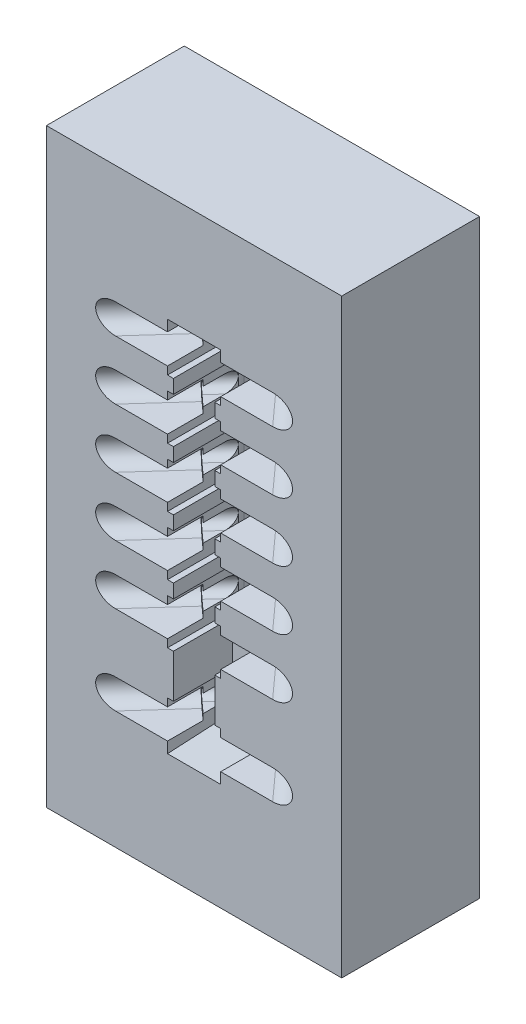
SolidWorks part; units mm, degrees
ref_plane "Front Plane" through (0, 0, 0) normal (0, 0, 1) x (1, 0, 0)
ref_plane "Top Plane" through (0, 0, 0) normal (0, 1, 0) x (1, 0, 0)
ref_plane "Right Plane" through (0, 0, 0) normal (1, 0, 0) x (0, 0, -1)
sketch "Sketch1" plane through (0, 0, 0) normal (0, 0, 1) x (1, 0, 0)
  line L0 (-7.5, 0) -> (0, 0) construction
  line L1 (-7.5, 15) -> (7.5, 15)
  line L2 (-7.5, 15) -> (-7.5, -15)
  line L3 (-7.5, -15) -> (7.5, -15)
  line L4 (7.5, 15) -> (7.5, -15)
  line L5 (0, 0) -> (0, 15) construction
  dimension "D1" = 15
  dimension "D2" = 30
sketch "Sketch2" plane through (0, 0, 0) normal (1, 0, 0) x (0, 0, -1)
  line L1 (0, 15) -> (7, 15)
  line L2 (0, 15) -> (0, -15)
  line L3 (0, -15) -> (7, -15)
  line L4 (7, 15) -> (7, -15)
  dimension "D1" = 7
extrude "Boss-Extrude1" add sketch "Sketch1" against normal up to vertex (7 mm away) up to point (0, 15, -7)
ref_plane "Plane1" through (1.35, 0, 0) normal (1, 0, 0) x (0, 0, -1)
sketch "Sketch7" plane through (1.35, 0, 0) normal (1, 0, 0) x (0, 0, -1)
  line L0 (3, 4.1005) -> (0, 4.1005) construction
  line L1 (0, 4.1005) -> (0, 6.3995) construction
  line L2 (3, 6.3995) -> (0, 6.3995) construction
  line L3 (3, 6.3995) -> (6.5, 6.2161) construction
  line L4 (6.5, 6.2161) -> (6.5, 4.2839) construction
  line L5 (6.5, 4.2839) -> (3, 4.1005) construction
  line L6 (3, 1.1005) -> (0, 1.1005) construction
  line L7 (0, 1.1005) -> (0, 3.3995) construction
  line L8 (3, 3.3995) -> (0, 3.3995) construction
  line L9 (6.5, 3.2161) -> (3, 3.3995) construction
  line L10 (6.5, 1.2839) -> (6.5, 3.2161) construction
  line L11 (3, 1.1005) -> (6.5, 1.2839) construction
  line L12 (3, -1.8995) -> (0, -1.8995) construction
  line L13 (0, -1.8995) -> (0, 0.3995) construction
  line L14 (3, 0.3995) -> (0, 0.3995) construction
  line L15 (3, 0.3995) -> (6.5, 0.2161) construction
  line L16 (6.5, 0.2161) -> (6.5, -1.7161) construction
  line L17 (6.5, -1.7161) -> (3, -1.8995) construction
  line L19 (3, -4.8995) -> (0, -4.8995) construction
  line L20 (0, -4.8995) -> (0, -2.6005) construction
  line L21 (3, -2.6005) -> (0, -2.6005) construction
  line L22 (6.5, -2.7839) -> (3, -2.6005) construction
  line L23 (6.5, -4.7161) -> (6.5, -2.7839) construction
  line L24 (3, -4.8995) -> (6.5, -4.7161) construction
  line L25 (3, -7.1005) -> (0, -7.1005) construction
  line L26 (0, -9.5567) -> (0, -7.1005) construction
  line L27 (6.5, -9.2161) -> (0, -9.5567) construction
  line L28 (6.5, -7.2839) -> (6.5, -9.2161) construction
  line L29 (3, -7.1005) -> (6.5, -7.2839) construction
  line L30 (3, 7.1005) -> (0, 7.1005) construction
  line L31 (0, 7.1005) -> (0, 9.5567) construction
  line L32 (6.5, 9.2161) -> (0, 9.5567) construction
  line L33 (6.5, 7.2839) -> (6.5, 9.2161) construction
  line L34 (3, 7.1005) -> (6.5, 7.2839) construction
  line L35 (3, 4.1005) -> (0, 4.1005)
  line L36 (0, 4.1005) -> (0, 6.3995)
  line L37 (3, 6.3995) -> (0, 6.3995)
  line L38 (3, 6.3995) -> (6.5, 6.2161)
  line L39 (6.5, 6.2161) -> (6.5, 4.2839)
  line L40 (6.5, 4.2839) -> (3, 4.1005)
  line L41 (3, 1.1005) -> (0, 1.1005)
  line L42 (0, 1.1005) -> (0, 3.3995)
  line L43 (3, 3.3995) -> (0, 3.3995)
  line L44 (6.5, 3.2161) -> (3, 3.3995)
  line L45 (6.5, 1.2839) -> (6.5, 3.2161)
  line L46 (3, 1.1005) -> (6.5, 1.2839)
  line L47 (3, -1.8995) -> (0, -1.8995)
  line L48 (0, -1.8995) -> (0, 0.3995)
  line L49 (3, 0.3995) -> (0, 0.3995)
  line L50 (3, 0.3995) -> (6.5, 0.2161)
  line L51 (6.5, 0.2161) -> (6.5, -1.7161)
  line L52 (6.5, -1.7161) -> (3, -1.8995)
  line L54 (3, -4.8995) -> (0, -4.8995)
  line L55 (0, -4.8995) -> (0, -2.6005)
  line L56 (3, -2.6005) -> (0, -2.6005)
  line L57 (6.5, -2.7839) -> (3, -2.6005)
  line L58 (6.5, -4.7161) -> (6.5, -2.7839)
  line L59 (3, -4.8995) -> (6.5, -4.7161)
  line L60 (3, -7.1005) -> (0, -7.1005)
  line L61 (0, -9.5567) -> (0, -7.1005)
  line L62 (6.5, -9.2161) -> (0, -9.5567)
  line L63 (6.5, -7.2839) -> (6.5, -9.2161)
  line L64 (3, -7.1005) -> (6.5, -7.2839)
  line L65 (3, 7.1005) -> (0, 7.1005)
  line L66 (0, 7.1005) -> (0, 9.5567)
  line L67 (6.5, 9.2161) -> (0, 9.5567)
  line L68 (6.5, 7.2839) -> (6.5, 9.2161)
  line L69 (3, 7.1005) -> (6.5, 7.2839)
sketch "Sketch8" plane through (1.35, 0, 0) normal (1, 0, 0) x (0, 0, -1)
  line L0 (6.5, -4.7161) -> (6.5, -2.7839) construction
  line L1 (6.5, -2.7839) -> (3, -2.6005) construction
  line L2 (3, -2.6005) -> (3, -1.8995) construction
  line L3 (6.5, -1.7161) -> (3, -1.8995) construction
  line L4 (6.5, 0.2161) -> (6.5, -1.7161) construction
  line L5 (3, 0.3995) -> (6.5, 0.2161) construction
  line L6 (3, 0.3995) -> (3, 1.1005) construction
  line L7 (3, 1.1005) -> (6.5, 1.2839) construction
  line L8 (6.5, 1.2839) -> (6.5, 3.2161) construction
  line L9 (6.5, 3.2161) -> (3, 3.3995) construction
  line L10 (3, 3.3995) -> (3, 4.1005) construction
  line L11 (6.5, 4.2839) -> (3, 4.1005) construction
  line L12 (6.5, 6.2161) -> (6.5, 4.2839) construction
  line L13 (3, 6.3995) -> (6.5, 6.2161) construction
  line L14 (3, 6.3995) -> (3, 7.1005) construction
  line L15 (3, 7.1005) -> (6.5, 7.2839) construction
  line L16 (6.5, 7.2839) -> (6.5, 9.2161) construction
  line L17 (6.5, 9.2161) -> (0, 9.5567) construction
  line L18 (0, 9.5567) -> (0, -9.5567) construction
  line L19 (6.5, -9.2161) -> (0, -9.5567) construction
  line L20 (6.5, -7.2839) -> (6.5, -9.2161) construction
  line L21 (3, -7.1005) -> (6.5, -7.2839) construction
  line L22 (3, -7.1005) -> (3, -4.8995) construction
  line L23 (3, -4.8995) -> (6.5, -4.7161) construction
  line L24 (6.5, -4.7161) -> (6.5, -2.7839)
  line L25 (6.5, -2.7839) -> (3, -2.6005)
  line L26 (3, -2.6005) -> (3, -1.8995)
  line L27 (6.5, -1.7161) -> (3, -1.8995)
  line L28 (6.5, 0.2161) -> (6.5, -1.7161)
  line L29 (3, 0.3995) -> (6.5, 0.2161)
  line L30 (3, 0.3995) -> (3, 1.1005)
  line L31 (3, 1.1005) -> (6.5, 1.2839)
  line L32 (6.5, 1.2839) -> (6.5, 3.2161)
  line L33 (6.5, 3.2161) -> (3, 3.3995)
  line L34 (3, 3.3995) -> (3, 4.1005)
  line L35 (6.5, 4.2839) -> (3, 4.1005)
  line L36 (6.5, 6.2161) -> (6.5, 4.2839)
  line L37 (3, 6.3995) -> (6.5, 6.2161)
  line L38 (3, 6.3995) -> (3, 7.1005)
  line L39 (3, 7.1005) -> (6.5, 7.2839)
  line L40 (6.5, 7.2839) -> (6.5, 9.2161)
  line L41 (6.5, 9.2161) -> (0, 9.5567)
  line L42 (0, 9.5567) -> (0, -9.5567)
  line L43 (6.5, -9.2161) -> (0, -9.5567)
  line L44 (6.5, -7.2839) -> (6.5, -9.2161)
  line L45 (3, -7.1005) -> (6.5, -7.2839)
  line L46 (3, -7.1005) -> (3, -4.8995)
  line L47 (3, -4.8995) -> (6.5, -4.7161)
sketch "Sketch9" plane through (0, 0, 0) normal (0, 0, 1) x (1, 0, 0)
  line L0 (-1.35, 9.5567) -> (-1.35, -9.5567) construction
  line L1 (1.35, -9.5567) -> (-1.35, -9.5567) construction
  line L2 (1.35, 9.5567) -> (1.35, -9.5567) construction
  line L3 (1.35, 9.5567) -> (-1.35, 9.5567) construction
  line L4 (-1.35, 9.5567) -> (-1.35, -9.5567) construction
  line L5 (1.35, -9.5567) -> (-1.35, -9.5567) construction
  line L6 (1.35, 9.5567) -> (1.35, -9.5567) construction
  line L7 (1.35, 9.5567) -> (-1.35, 9.5567) construction
  line L8 (0, -9.5567) -> (0, 9.5567) construction
  line L9 (-1.35, 0) -> (1.35, 0) construction
  line L10 (0.75, -9.1562) -> (-0.75, -9.1562) construction
  line L11 (-0.75, 9.1562) -> (-0.75, -9.1562) construction
  line L12 (0.75, 9.1562) -> (-0.75, 9.1562) construction
  line L13 (0.75, -9.1562) -> (-0.75, -9.1562)
  line L14 (-0.75, 9.1562) -> (-0.75, -9.1562)
  line L15 (0.75, 9.1562) -> (-0.75, 9.1562)
  line L16 (0.75, -9.1562) -> (0.75, 9.1562)
  line L17 (1.05, -9.5567) -> (1.05, 9.5567) construction
  line L18 (-1.05, -9.5567) -> (-1.05, 9.5567) construction
  line L19 (1.05, -9.5567) -> (1.05, 9.5567) construction
  line L20 (-1.05, -9.5567) -> (-1.05, 9.5567) construction
ref_plane "Plane2" through (0, -9.5567, 0) normal (0, 1, 0) x (1, 0, 0)
sketch "Sketch10" plane through (0, -9.5567, 0) normal (0, 1, 0) x (1, 0, 0)
  line L0 (1.35, 3.5995) -> (1.35, 6.5)
  line L1 (-1.35, 3.5995) -> (-1.35, 6.5)
  arc A0 (-1.2465, 3.7776) -> (-1.35, 6.5) centre (-4.95, 5) ccw construction
  arc A1 (-1.35, 3.5995) -> (-1.2465, 3.7776) centre (-1.7213, 3.9344) ccw construction
  arc A2 (1.2465, 3.7776) -> (1.35, 3.5995) centre (1.7213, 3.9344) ccw construction
  arc A3 (1.35, 6.5) -> (1.2465, 3.7776) centre (4.95, 5) ccw construction
  arc A4 (-1.2465, 3.7776) -> (-1.35, 6.5) centre (-4.95, 5) ccw
  arc A5 (-1.35, 3.5995) -> (-1.2465, 3.7776) centre (-1.7213, 3.9344) ccw
  arc A6 (1.2465, 3.7776) -> (1.35, 3.5995) centre (1.7213, 3.9344) ccw
  arc A7 (1.35, 6.5) -> (1.2465, 3.7776) centre (4.95, 5) ccw
ref_plane "Plane3" through (2.213, 9.1562, -4.3777) normal (0.6697, 0, 0.7426) x (0, -1, 0)
sketch "Sketch11" plane through (2.213, 9.1562, -4.3777) normal (0.6697, 0, 0.7426) x (0, -1, 0)
  line L0 (0.4562, -2.362) -> (0.4562, -1.612) construction
  line L1 (1.3562, -1.612) -> (1.3562, -2.362) construction
  line L2 (1.3562, -2.362) -> (0.4562, -2.362) construction
  line L3 (3.4562, -1.612) -> (3.4562, -2.362) construction
  line L4 (3.4562, -2.362) -> (4.3562, -2.362) construction
  line L5 (4.3562, -2.362) -> (4.3562, -1.612) construction
  line L6 (7.3562, -1.612) -> (7.3562, -2.362) construction
  line L7 (7.3562, -2.362) -> (6.4562, -2.362) construction
  line L8 (6.4562, -2.362) -> (6.4562, -1.612) construction
  line L9 (9.4562, -1.612) -> (9.4562, -2.362) construction
  line L10 (9.4562, -2.362) -> (10.3562, -2.362) construction
  line L11 (10.3562, -2.362) -> (10.3562, -1.612) construction
  line L12 (13.3562, -1.612) -> (13.3562, -2.362) construction
  line L13 (13.3562, -2.362) -> (12.4562, -2.362) construction
  line L14 (12.4562, -2.362) -> (12.4562, -1.612) construction
  line L15 (16.9562, -1.612) -> (16.9562, -2.362) construction
  line L16 (16.9562, -2.362) -> (17.8562, -2.362) construction
  line L17 (17.8562, -2.362) -> (17.8562, -1.612) construction
  line L18 (0.4562, -2.362) -> (0.4562, -1.612)
  line L19 (1.3562, -1.612) -> (1.3562, -2.362)
  line L20 (1.3562, -2.362) -> (0.4562, -2.362)
  line L21 (3.4562, -1.612) -> (3.4562, -2.362)
  line L22 (3.4562, -2.362) -> (4.3562, -2.362)
  line L23 (4.3562, -2.362) -> (4.3562, -1.612)
  line L24 (7.3562, -1.612) -> (7.3562, -2.362)
  line L25 (7.3562, -2.362) -> (6.4562, -2.362)
  line L26 (6.4562, -2.362) -> (6.4562, -1.612)
  line L27 (9.4562, -1.612) -> (9.4562, -2.362)
  line L28 (9.4562, -2.362) -> (10.3562, -2.362)
  line L29 (10.3562, -2.362) -> (10.3562, -1.612)
  line L30 (13.3562, -1.612) -> (13.3562, -2.362)
  line L31 (13.3562, -2.362) -> (12.4562, -2.362)
  line L32 (12.4562, -2.362) -> (12.4562, -1.612)
  line L33 (16.9562, -1.612) -> (16.9562, -2.362)
  line L34 (16.9562, -2.362) -> (17.8562, -2.362)
  line L35 (17.8562, -2.362) -> (17.8562, -1.612)
  line L36 (0.9062, -1.612) -> (0.9062, -1.162) construction
  line L37 (3.9062, -1.162) -> (3.9062, -1.612) construction
  line L38 (6.9062, -1.612) -> (6.9062, -1.162) construction
  line L39 (9.9062, -1.612) -> (9.9062, -1.162) construction
  line L40 (12.9062, -1.612) -> (12.9062, -1.162) construction
  line L41 (17.4062, -1.612) -> (17.4062, -1.162) construction
  line L42 (17.8562, -1.612) -> (16.9562, -1.612) construction
  line L43 (13.3562, -1.612) -> (12.4562, -1.612) construction
  line L44 (10.3562, -1.612) -> (9.4562, -1.612) construction
  line L46 (7.3562, -1.612) -> (6.4562, -1.612) construction
  line L47 (4.3562, -1.612) -> (3.4562, -1.612) construction
  line L48 (1.3562, -1.612) -> (0.4562, -1.612) construction
  arc A0 (1.3562, -1.612) -> (0.4562, -1.612) centre (0.9062, -1.612) ccw construction
  arc A1 (4.3562, -1.612) -> (3.4562, -1.612) centre (3.9062, -1.612) ccw construction
  arc A2 (7.3562, -1.612) -> (6.4562, -1.612) centre (6.9062, -1.612) ccw construction
  arc A3 (10.3562, -1.612) -> (9.4562, -1.612) centre (9.9062, -1.612) ccw construction
  arc A4 (13.3562, -1.612) -> (12.4562, -1.612) centre (12.9062, -1.612) ccw construction
  arc A5 (17.8562, -1.612) -> (16.9562, -1.612) centre (17.4062, -1.612) ccw construction
  arc A6 (1.3562, -1.612) -> (0.4562, -1.612) centre (0.9062, -1.612) ccw
  arc A7 (4.3562, -1.612) -> (3.4562, -1.612) centre (3.9062, -1.612) ccw
  arc A8 (7.3562, -1.612) -> (6.4562, -1.612) centre (6.9062, -1.612) ccw
  arc A9 (10.3562, -1.612) -> (9.4562, -1.612) centre (9.9062, -1.612) ccw
  arc A10 (13.3562, -1.612) -> (12.4562, -1.612) centre (12.9062, -1.612) ccw
  arc A11 (17.8562, -1.612) -> (16.9562, -1.612) centre (17.4062, -1.612) ccw
ref_plane "Plane4" through (3.1041, 9.1562, -3.3895) normal (0.6697, 0, 0.7426) x (0, -1, 0)
sketch "Sketch12" plane through (3.1041, 9.1562, -3.3895) normal (0.6697, 0, 0.7426) x (0, -1, 0)
  line L0 (0.1562, -1.612) -> (0.1562, -5.0612) construction
  line L1 (0.1562, -5.0612) -> (1.6562, -5.0612) construction
  line L2 (1.6562, -1.612) -> (1.6562, -5.0612) construction
  line L3 (3.1562, -1.612) -> (3.1562, -5.0612) construction
  line L4 (4.6562, -5.0612) -> (3.1562, -5.0612) construction
  line L5 (4.6562, -1.612) -> (4.6562, -5.0612) construction
  line L6 (6.1562, -1.612) -> (6.1562, -5.0612) construction
  line L7 (6.1562, -5.0612) -> (7.6562, -5.0612) construction
  line L8 (7.6562, -1.612) -> (7.6562, -5.0612) construction
  line L9 (9.1562, -1.612) -> (9.1562, -5.0612) construction
  line L10 (10.6562, -5.0612) -> (9.1562, -5.0612) construction
  line L11 (10.6562, -1.612) -> (10.6562, -5.0612) construction
  line L12 (12.1562, -1.612) -> (12.1562, -5.0612) construction
  line L13 (12.1562, -5.0612) -> (13.6562, -5.0612) construction
  line L14 (13.6562, -1.612) -> (13.6562, -5.0612) construction
  line L15 (16.6562, -1.612) -> (16.6562, -5.0612) construction
  line L16 (18.1562, -5.0612) -> (16.6562, -5.0612) construction
  line L17 (18.1562, -1.612) -> (18.1562, -5.0612) construction
  line L18 (0.1562, -1.612) -> (0.1562, -5.0612)
  line L19 (0.1562, -5.0612) -> (1.6562, -5.0612)
  line L20 (1.6562, -1.612) -> (1.6562, -5.0612)
  line L21 (3.1562, -1.612) -> (3.1562, -5.0612)
  line L22 (4.6562, -5.0612) -> (3.1562, -5.0612)
  line L23 (4.6562, -1.612) -> (4.6562, -5.0612)
  line L24 (6.1562, -1.612) -> (6.1562, -5.0612)
  line L25 (6.1562, -5.0612) -> (7.6562, -5.0612)
  line L26 (7.6562, -1.612) -> (7.6562, -5.0612)
  line L27 (9.1562, -1.612) -> (9.1562, -5.0612)
  line L28 (10.6562, -5.0612) -> (9.1562, -5.0612)
  line L29 (10.6562, -1.612) -> (10.6562, -5.0612)
  line L30 (12.1562, -1.612) -> (12.1562, -5.0612)
  line L31 (12.1562, -5.0612) -> (13.6562, -5.0612)
  line L32 (13.6562, -1.612) -> (13.6562, -5.0612)
  line L33 (16.6562, -1.612) -> (16.6562, -5.0612)
  line L34 (18.1562, -5.0612) -> (16.6562, -5.0612)
  line L35 (18.1562, -1.612) -> (18.1562, -5.0612)
  line L36 (16.6562, -1.612) -> (18.1562, -1.612) construction
  line L37 (12.1562, -1.612) -> (13.6562, -1.612) construction
  line L38 (10.6562, -1.612) -> (9.1562, -1.612) construction
  line L39 (7.6562, -1.612) -> (6.1562, -1.612) construction
  line L40 (4.6562, -1.612) -> (3.1562, -1.612) construction
  line L41 (1.6562, -1.612) -> (0.1562, -1.612) construction
  line L42 (0.9062, -1.612) -> (0.9062, -0.862) construction
  line L43 (3.9062, -0.862) -> (3.9062, -1.612) construction
  line L44 (6.9062, -0.862) -> (6.9062, -1.612) construction
  line L45 (9.9062, -0.862) -> (9.9062, -1.612) construction
  line L46 (12.9062, -0.862) -> (12.9062, -1.612) construction
  line L47 (17.4062, -0.862) -> (17.4062, -1.612) construction
  arc A0 (1.6562, -1.612) -> (0.1562, -1.612) centre (0.9062, -1.612) ccw construction
  arc A1 (4.6562, -1.612) -> (3.1562, -1.612) centre (3.9062, -1.612) ccw construction
  arc A2 (7.6562, -1.612) -> (6.1562, -1.612) centre (6.9062, -1.612) ccw construction
  arc A3 (10.6562, -1.612) -> (9.1562, -1.612) centre (9.9062, -1.612) ccw construction
  arc A4 (13.6562, -1.612) -> (12.1562, -1.612) centre (12.9062, -1.612) ccw construction
  arc A5 (18.1562, -1.612) -> (16.6562, -1.612) centre (17.4062, -1.612) ccw construction
  arc A6 (1.6562, -1.612) -> (0.1562, -1.612) centre (0.9062, -1.612) ccw
  arc A7 (4.6562, -1.612) -> (3.1562, -1.612) centre (3.9062, -1.612) ccw
  arc A8 (7.6562, -1.612) -> (6.1562, -1.612) centre (6.9062, -1.612) ccw
  arc A9 (10.6562, -1.612) -> (9.1562, -1.612) centre (9.9062, -1.612) ccw
  arc A10 (13.6562, -1.612) -> (12.1562, -1.612) centre (12.9062, -1.612) ccw
  arc A11 (18.1562, -1.612) -> (16.6562, -1.612) centre (17.4062, -1.612) ccw
extrude "Cut-Extrude1" cut sketch "Sketch8" against normal up to vertex (2.4 mm away) from vertex up to point (-1.05, -9.5567, 0) starting at point (1.05, -9.5567, 0)
extrude "Cut-Extrude4" cut sketch "Sketch7" against normal up to vertex (2.7 mm away) up to point (-1.35, -9.5567, 0)
extrude "Boss-Extrude2" add sketch "Sketch10" along normal up to vertex (19.1135 mm away) up to point (-1.35, 9.5567, 0)
extrude "Cut-Extrude2" cut sketch "Sketch12" along normal through all
extrude "Cut-Extrude3" cut sketch "Sketch11" along normal through all
mirror "Mirror1" about plane through (0, 0, 0) normal (1, 0, 0) of "Cut-Extrude2", "Cut-Extrude3"
sketch "Sketch13" plane through (0, 0, 0) normal (0, 0, 1) x (1, 0, 0)
  line L0 (0, 0) -> (-5, 0) construction
  line L1 (-5, -10) -> (5, -10)
  line L2 (-5, -10) -> (-5, 10)
  line L3 (-5, 10) -> (5, 10)
  line L4 (5, -10) -> (5, 10)
  line L5 (0, 0) -> (5, 0) construction
  line L6 (0, 10) -> (0, 0) construction
  line L7 (0, -10) -> (0, 0) construction
  dimension "D1" = 10
  dimension "D2" = 20
sketch "Sketch15" plane through (0, -9.5567, 0) normal (0, 1, 0) x (1, 0, 0)
  line L0 (1.907, 2.3099) -> (-0.6545, 0) construction
  line L1 (1.907, 2.3099) -> (-0.6545, 0)
  line L2 (0, 0) -> (0, 3.5995) construction
  line L3 (-1.35, 0) -> (1.35, 0) construction
  line L4 (-0.6545, 0) -> (0.6545, 0) construction
  line L5 (-1.907, 2.3099) -> (0.6545, 0)
  line L6 (1.907, 2.3099) -> (-1.907, 2.3099) construction
  line L7 (1.907, 2.3099) -> (2.4639, 2.8122) construction
  line L8 (-1.907, 2.3099) -> (-2.4639, 2.8122) construction
  line L9 (-2.4639, 2.8122) -> (2.4639, 2.8122) construction
  line L10 (0.4588, 2.7959) -> (1.0158, 3.2981)
  line L11 (1.0158, 3.2981) -> (1.35, 3.5995) construction
  line L12 (1.35, 3.5995) -> (-1.35, 3.5995) construction
  line L13 (-1.35, 3.5995) -> (-1.0158, 3.2981) construction
  line L14 (-1.0158, 3.2981) -> (-0.477, 2.8122)
  line L15 (-1.0158, 3.2981) -> (1.0158, 3.2981) construction
ref_plane "Plane5" through (0, 9.5567, 0) normal (0, 1, 0) x (1, 0, 0)
sketch "Sketch16" plane through (0, 9.5567, 0) normal (0, 1, 0) x (1, 0, 0)
  line L0 (-1.907, 2.3099) -> (0.6545, 0) construction
  line L1 (-1.907, 2.3099) -> (0.6545, 0)
  line L2 (-1.0158, 3.2981) -> (-0.477, 2.8122) construction
  line L3 (-1.0158, 3.2981) -> (-0.477, 2.8122)
ref_plane "Plane6" through (0.2935, 0, -0.3255) normal (-0.6697, 0, 0.7426) x (0.7426, 0, 0.6697)
ref_plane "Plane7" through (1.1847, 0, -1.3137) normal (-0.6697, 0, 0.7426) x (0.7426, 0, 0.6697)
sketch "Sketch17" plane through (0.2935, 0, -0.3255) normal (-0.6697, 0, 0.7426) x (0.7426, 0, 0.6697)
  line L0 (0.4861, -9.5567) -> (0.4861, 9.5567) construction
  line L1 (-2.9631, 9.5567) -> (-2.9631, -9.5567) construction
  line L2 (-2.9631, -9.5567) -> (-3.7131, -9.5567) construction
  line L3 (-3.7131, -9.5567) -> (-3.7131, 9.5567) construction
  line L4 (-3.7131, 9.5567) -> (-2.9631, 9.5567) construction
  line L5 (-2.9631, 9.5567) -> (0.4861, 9.5567) construction
  line L6 (-2.9631, -9.5567) -> (0.4861, -9.5567) construction
  line L7 (-0.0536, -8.25) -> (-0.1308, -8.25) construction
  line L8 (-0.0536, -3.75) -> (-0.1308, -3.75) construction
  line L9 (-0.0536, -0.75) -> (-0.1308, -0.75) construction
  line L10 (-0.0536, 2.25) -> (-0.1308, 2.25) construction
  line L11 (-0.0536, 5.25) -> (-0.1308, 5.25) construction
  line L12 (-0.1308, 8.25) -> (-0.0536, 8.25) construction
  line L13 (-2.9631, 9) -> (0.4861, 9)
  line L14 (0.4861, 9) -> (0.4861, 7.5)
  line L15 (0.4861, 7.5) -> (-2.9631, 7.5)
  line L16 (-2.9631, 6) -> (0.4861, 6)
  line L17 (0.4861, 6) -> (0.4861, 4.5)
  line L18 (0.4861, 4.5) -> (-2.9631, 4.5)
  line L19 (-2.9631, -9) -> (0.4861, -9)
  line L20 (0.4861, -9) -> (0.4861, -7.5)
  line L21 (0.4861, -7.5) -> (-2.9631, -7.5)
  line L22 (-2.9631, -4.5) -> (0.4861, -4.5)
  line L23 (0.4861, -4.5) -> (0.4861, -3)
  line L24 (0.4861, -3) -> (-2.9631, -3)
  line L25 (-2.9631, 0) -> (0.4861, 0)
  line L26 (0.4861, 0) -> (0.4861, -1.5)
  line L27 (0.4861, -1.5) -> (-2.9631, -1.5)
  line L28 (-2.9631, 3) -> (0.4861, 3)
  line L29 (0.4861, 3) -> (0.4861, 1.5)
  line L30 (0.4861, 1.5) -> (-2.9631, 1.5)
  line L31 (-0.1308, 4.5) -> (-0.4861, 4.5) construction
  line L32 (-0.1308, 6) -> (-0.4861, 6) construction
  circle A0 centre (-2.9631, -8.25) radius 0.75 construction
  circle A1 centre (-2.9631, 8.25) radius 0.75 construction
  circle A2 centre (-2.9631, 5.25) radius 0.75 construction
  circle A3 centre (-2.9631, 2.25) radius 0.75 construction
  circle A4 centre (-2.9631, -0.75) radius 0.75 construction
  circle A5 centre (-2.9631, -3.75) radius 0.75 construction
  arc A6 (-2.9631, 9) -> (-2.9631, 7.5) centre (-2.9631, 8.25) ccw
  arc A7 (-2.9631, 6) -> (-2.9631, 4.5) centre (-2.9631, 5.25) ccw
  arc A8 (-2.9631, 3) -> (-2.9631, 1.5) centre (-2.9631, 2.25) ccw
  arc A9 (-2.9631, -7.5) -> (-2.9631, -9) centre (-2.9631, -8.25) ccw
  arc A10 (-2.9631, -3) -> (-2.9631, -4.5) centre (-2.9631, -3.75) ccw
  arc A11 (-2.9631, 0) -> (-2.9631, -1.5) centre (-2.9631, -0.75) ccw
sketch "Sketch18" plane through (1.1847, 0, -1.3137) normal (-0.6697, 0, 0.7426) x (0.7426, 0, 0.6697)
  line L1 (-2.2376, -9.5567) -> (-2.9631, -9.5567) construction
  line L2 (-2.2376, -9.5567) -> (-2.2376, 9.5567) construction
  line L3 (-2.2376, 9.5567) -> (-2.9631, 9.5567) construction
  line L4 (-2.9631, -9.5567) -> (-2.9631, 9.5567) construction
  line L6 (-2.9631, -9.5567) -> (-3.4131, -9.5567) construction
  line L7 (-3.4131, -9.5567) -> (-3.4131, 9.5567) construction
  line L8 (-3.4131, 9.5567) -> (-2.9631, 9.5567) construction
  line L9 (-1.4544, 8.25) -> (-1.408, 8.25) construction
  line L10 (-1.4544, 2.25) -> (-1.408, 2.25) construction
  line L11 (-1.408, 5.25) -> (-1.4544, 5.25) construction
  line L12 (-2.9631, 8.7) -> (-2.2376, 8.7)
  line L13 (-2.2376, 8.7) -> (-2.2376, 7.8)
  line L14 (-2.2376, 7.8) -> (-2.9631, 7.8)
  line L15 (-2.9631, 5.7) -> (-2.2376, 5.7)
  line L16 (-2.2376, 5.7) -> (-2.2376, 4.8)
  line L17 (-2.2376, 4.8) -> (-2.9631, 4.8)
  line L18 (-2.9631, 2.7) -> (-2.2376, 2.7)
  line L19 (-2.2376, 2.7) -> (-2.2376, 1.8)
  line L20 (-2.2376, 1.8) -> (-2.9631, 1.8)
  line L21 (-1.4544, -3.75) -> (-1.408, -3.75) construction
  line L22 (-1.4544, -0.75) -> (-1.408, -0.75) construction
  line L23 (-2.9631, -0.3) -> (-2.2376, -0.3)
  line L24 (-2.2376, -0.3) -> (-2.2376, -1.2)
  line L25 (-2.2376, -1.2) -> (-2.9631, -1.2)
  line L26 (-2.9631, -3.3) -> (-2.2376, -3.3)
  line L27 (-2.2376, -3.3) -> (-2.2376, -4.2)
  line L28 (-2.2376, -4.2) -> (-2.9631, -4.2)
  line L29 (-2.9631, -7.8) -> (-2.2376, -7.8)
  line L30 (-2.2376, -7.8) -> (-2.2376, -8.7)
  line L31 (-2.2376, -8.7) -> (-2.9631, -8.7)
  line L32 (-1.4544, -8.25) -> (-1.408, -8.25) construction
  arc A0 (-2.9631, 8.7) -> (-2.9631, 7.8) centre (-2.9631, 8.25) ccw
  arc A1 (-2.9631, 5.7) -> (-2.9631, 4.8) centre (-2.9631, 5.25) ccw
  arc A2 (-2.9631, 2.7) -> (-2.9631, 1.8) centre (-2.9631, 2.25) ccw
  arc A3 (-2.9631, -0.3) -> (-2.9631, -1.2) centre (-2.9631, -0.75) ccw
  arc A4 (-2.9631, -3.3) -> (-2.9631, -4.2) centre (-2.9631, -3.75) ccw
  arc A5 (-2.9631, -7.8) -> (-2.9631, -8.7) centre (-2.9631, -8.25) ccw
